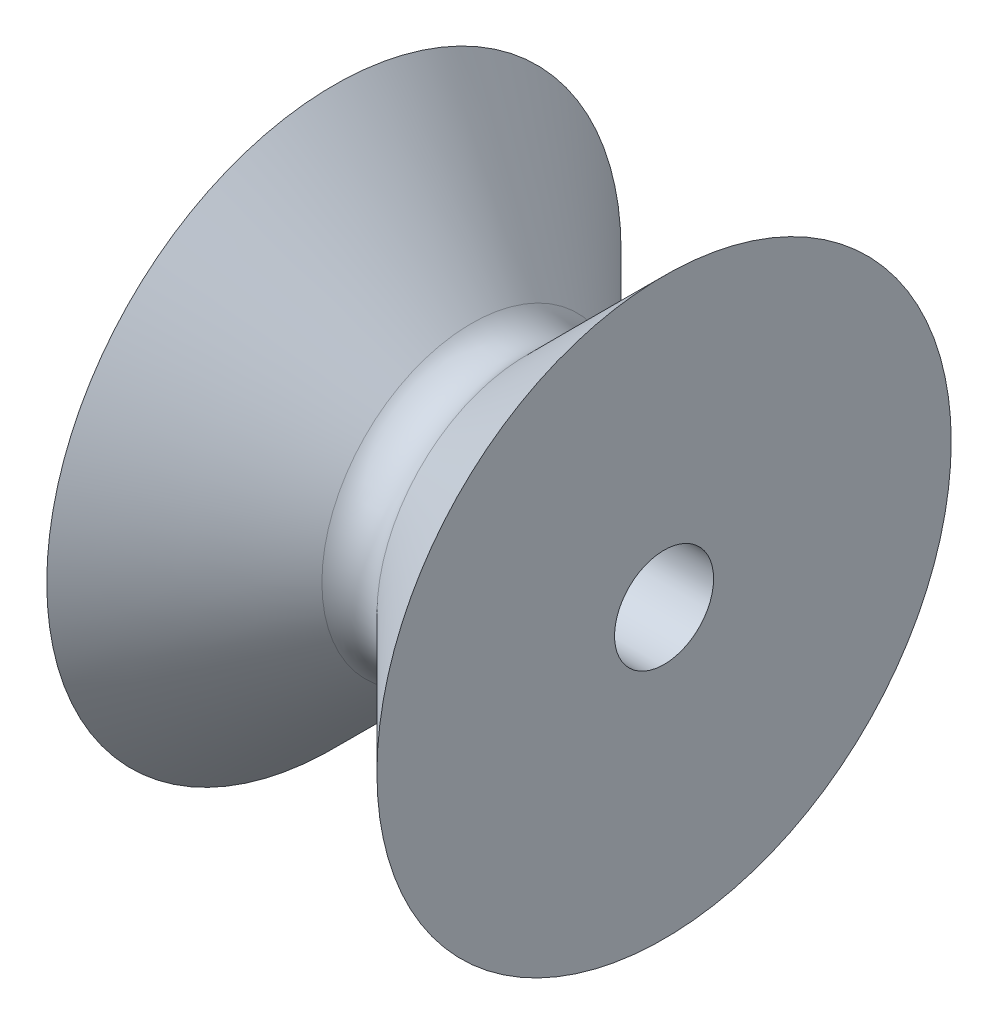
SolidWorks part; units mm, degrees
ref_plane "Front Plane" through (0, 0, 0) normal (0, 0, 1) x (1, 0, 0)
ref_plane "Top Plane" through (0, 0, 0) normal (0, 1, 0) x (1, 0, 0)
ref_plane "Right Plane" through (0, 0, 0) normal (1, 0, 0) x (0, 0, -1)
sketch "Sketch1" plane through (0, 0, 0) normal (1, 0, 0) x (0, 0, -1)
  circle A0 centre (0, 0) radius 17.5
  dimension "D1" = 35
extrude "Boss-Extrude1" add sketch "Sketch1" along normal blind 18
sketch "Sketch2" plane through (18, 0, 0) normal (1, 0, 0) x (0, 0, -1)
  circle A0 centre (0, 0) radius 2.7
  dimension "D1" = 5.4
extrude "Cut-Extrude1" cut sketch "Sketch2" against normal blind 18
sketch "Sketch3" plane through (0, 0, 0) normal (0, 0, 1) x (1, 0, 0)
  line L0 (0, 0) -> (18, 0) construction
  line L1 (18, -17.5) -> (18, 17.5) construction
  line L2 (9, 0) -> (9, 8.1556) construction
  line L3 (7.5, 8.1556) -> (10.5, 8.1556) construction
  line L4 (10.5, 8.1556) -> (24.9008, 22.5564)
  line L5 (7.5, 8.1556) -> (-6.9008, 22.5564)
  line L6 (-6.9008, 22.5564) -> (24.9008, 22.5564)
  line L7 (9, 8.1556) -> (9, 17.7082) construction
  line L8 (18, 17.5) -> (0, 17.5) construction
  arc A0 (7.5, 8.1556) -> (10.5, 8.1556) centre (9, 9.6556) ccw
  point P10 (9, 8.1556)
  point P13 (18, 18.3569)
  point P17 (9, 22.5564)
  dimension "D1" = 3
  dimension "D2" = 90
ref_axis "Axis1" through (0, 0, 0) along (1, 0, 0)
revolve "Cut-Revolve1" cut sketch "Sketch3" angle 360 about L0
